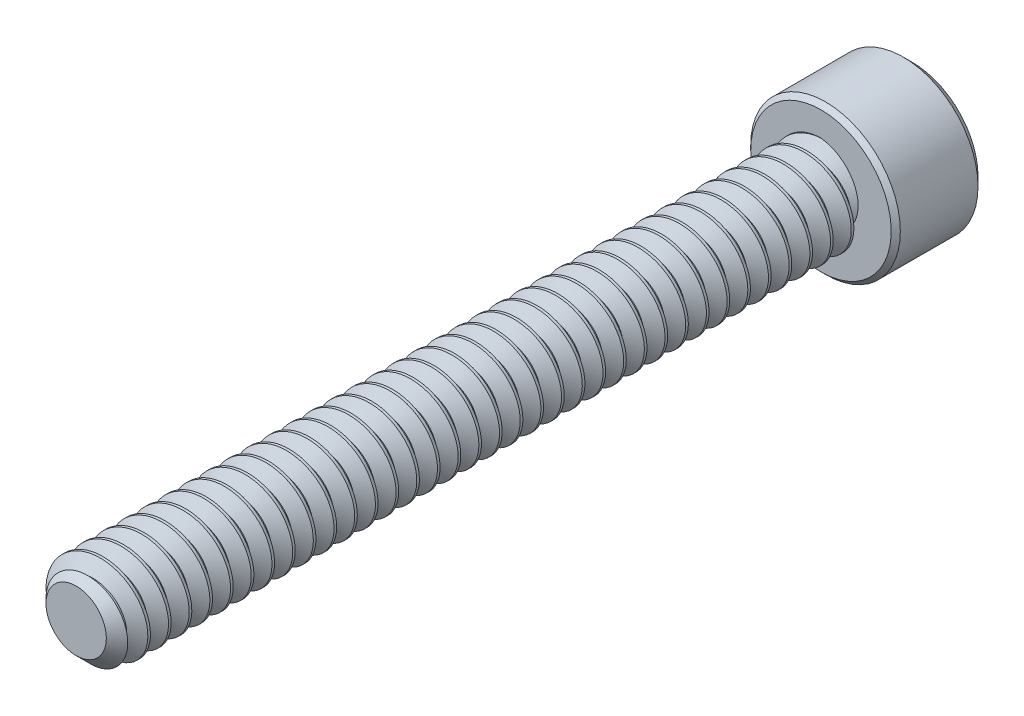
SolidWorks part; units mm, degrees
ref_plane "Front Plane" through (0, 0, 0) normal (0, 0, 1) x (1, 0, 0)
ref_plane "Top Plane" through (0, 0, 0) normal (0, 1, 0) x (1, 0, 0)
ref_plane "Right Plane" through (0, 0, 0) normal (1, 0, 0) x (0, 0, -1)
sketch "Sketch1" plane through (0, 0, 0) normal (0, 0, 1) x (1, 0, 0)
  line L0 (0, 1.7526) -> (0, -1.7526) construction
  circle A0 centre (0, 0) radius 1.7526
  dimension "OD" = 3.5052
extrude "Extrude1" add sketch "Sketch1" against normal blind 28.575
sketch "Sketch2" plane through (0, 0, 0) normal (0, 0, 1) x (1, 0, 0)
  circle A0 centre (0, 0) radius 1.7526 construction
  circle A1 centre (0, 0) radius 1.7526
curve "Helix/Spiral1" pitch 0.7937 height 29.3687 turns 37 parameters "pitch"=0.7937
chamfer "Chamfer3" distance 0.5953 angle 45 1 edges at (1.7526, 0, 0)
sketch "Sketch3" plane through (0, 0, 0) normal (1, 0, 0) x (0, 0, -1)
  line L0 (-0.6945, 1.7526) -> (-0.3969, 1.237)
  line L1 (-0.3969, 1.237) -> (-0.2977, 1.237)
  line L2 (-0.2977, 1.237) -> (0, 1.7526)
  line L3 (-0.6945, 1.7526) -> (0, 1.7526)
  line L4 (-0.3473, 1.7526) -> (-0.3473, 1.237) construction
  line L5 (-0.5457, 1.4948) -> (-0.1488, 1.4948) construction
  line L6 (0, 1.7526) -> (0, -1.7526) construction
  dimension "D1" = 0.0992
  dimension "D2" = 0.3969
  dimension "D3" = 60
sweep "Cut-Sweep1" cut profiles "Sketch3" path "Helix/Spiral1"
sketch "Sketch6" plane through (0, 0, -28.575) normal (0, 0, -1) x (-1, 0, 0)
  circle A0 centre (0, 0) radius 2.8702
  dimension "head dia" = 5.7404
extrude "Extrude2" add sketch "Sketch6" along normal blind 3.5052
sketch "Sketch7" plane through (0, 0, -32.0802) normal (0, 0, -1) x (-1, 0, 0)
  line L1 (0, 1.604) -> (-1.3891, 0.802)
  line L2 (-1.3891, 0.802) -> (-1.3891, -0.802)
  line L3 (-1.3891, -0.802) -> (0, -1.604)
  line L4 (0, -1.604) -> (1.3891, -0.802)
  line L5 (1.3891, -0.802) -> (1.3891, 0.802)
  line L6 (1.3891, 0.802) -> (0, 1.604)
  circle A0 centre (0, 0) radius 1.3891 construction
  dimension "hex dia" = 2.7781
extrude "Cut-Extrude1" cut sketch "Sketch7" against normal blind 2.0836
sketch "Sketch8" plane through (0, 0, -32.0802) normal (0, 0, -1) x (-1, 0, 0)
  circle A0 centre (0, 0) radius 1.604
extrude "Cut-Extrude2" cut sketch "Sketch8" against normal blind 0.3505 draft 45
chamfer "Chamfer1" distance 0.3505 angle 45 1 edges at (-2.8702, 0, -32.0802)
chamfer "Chamfer2" distance 0.1753 angle 45 1 edges at (-2.8702, 0, -28.575)
sketch "Sketch9" plane through (0, 0, 0) normal (1, 0, 0) x (0, 0, -1)
  line L0 (0, 1.7526) -> (0, -1.7526) construction
  line L1 (4.3656, 1.7526) -> (4.3656, -1.7526) construction
  line L2 (28.575, 2.8702) -> (28.575, -2.8702) construction
  line L3 (32.0802, 2.8702) -> (32.0802, -2.8702) construction
  line L4 (32.0802, 0) -> (0, 0) construction
  dimension "D1" = 4.3656
  dimension "D2" = 3.5052
  dimension "D3" = 5.7404
  dimension "D4" = 28.575
equation "\"D3@Helix/Spiral1\" = \"screw length@Extrude1\"+\"pitch@Helix/Spiral1\""
equation "\"D1@Sketch3\" = \"pitch@Helix/Spiral1\"*.125"
equation "\"D2@Sketch3\" = \"pitch@Helix/Spiral1\"*.5"
equation "\"D1@Cut-Extrude1\" = \"hex dia@Sketch7\"*.75"
equation "\"D1@Chamfer1\" = \"head depth@Extrude2\"/10"
equation "\"D1@Sketch9\" = \"pitch@Helix/Spiral1\"*5.5"
equation "\"D1@Chamfer2\" = \"D1@Chamfer1\"/2"
equation "\"D1@Cut-Extrude2\" = \"D1@Chamfer2\"*2"
equation "\"D1@Chamfer3\" = \"pitch@Helix/Spiral1\"*.750"
equation "\"D2@Sketch9\" = \"head depth@Extrude2\""
equation "\"D3@Sketch9\" = \"head dia@Sketch6\""
equation "\"D4@Sketch9\" = \"screw length@Extrude1\""
